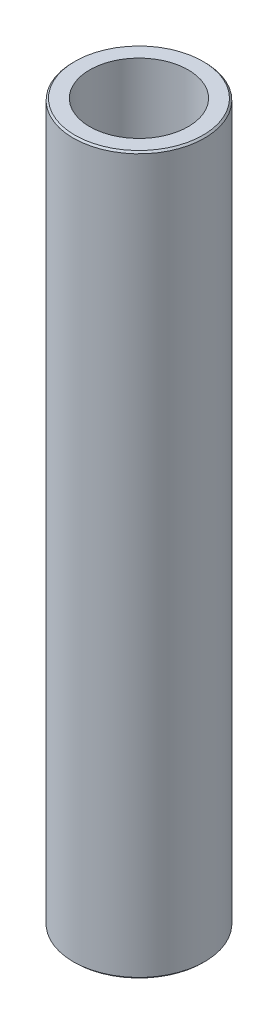
SolidWorks part; units mm, degrees
ref_plane "Front Plane" through (0, 0, 0) normal (0, 0, 1) x (1, 0, 0)
ref_plane "Top Plane" through (0, 0, 0) normal (0, 1, 0) x (1, 0, 0)
ref_plane "Right Plane" through (0, 0, 0) normal (1, 0, 0) x (0, 0, -1)
sketch "Sketch1" plane through (0, 0, 0) normal (0, 1, 0) x (1, 0, 0)
  circle A0 centre (0, 0) radius 55
  dimension "SHAFT_OD" = 110
extrude "Boss-Extrude1" add sketch "Sketch1" along normal blind 600
sketch "Sketch2" plane through (0, 0, 0) normal (0, 1, 0) x (1, 0, 0)
  circle A0 centre (0, 0) radius 41.2361
  dimension "BORE_D" = 82.4722
extrude "Cut-Extrude1" cut sketch "Sketch2" along normal through all
chamfer "Chamfer1" distance 1.4025 angle 45 2 edges at (0, 600, 55) (0, 0, 55)
